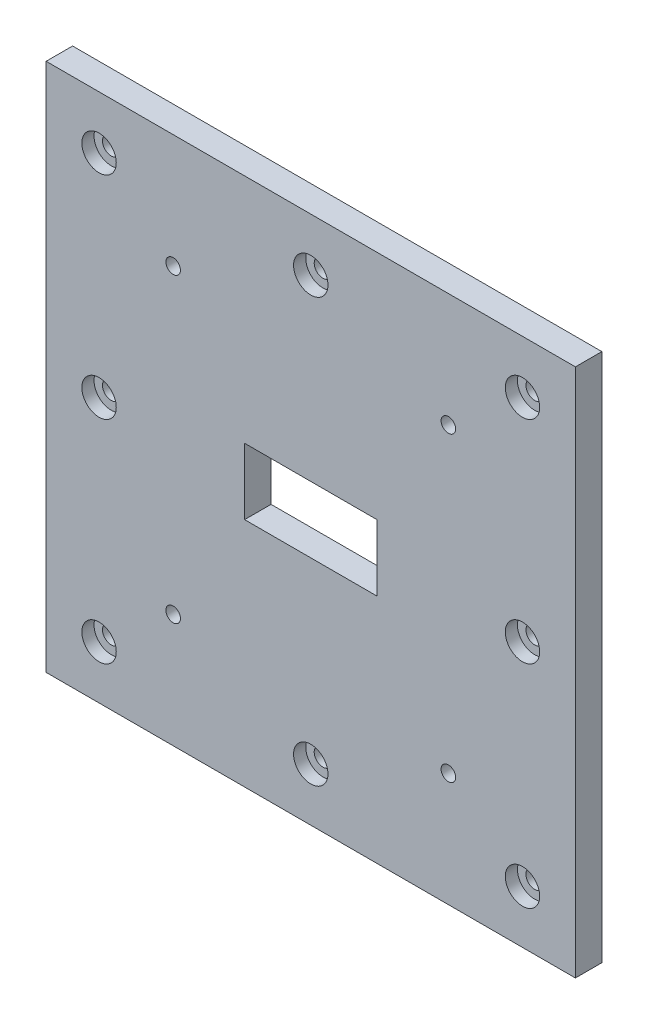
SolidWorks part; units mm, degrees
material "Aluminum"
ref_plane "Front Plane" through (0, 0, 0) normal (0, 0, 1) x (1, 0, 0)
ref_plane "Top Plane" through (0, 0, 0) normal (0, 1, 0) x (1, 0, 0)
ref_plane "Right Plane" through (0, 0, 0) normal (1, 0, 0) x (0, 0, -1)
sketch "Sketch1" plane through (0, 0, 0) normal (0, 0, 1) x (1, 0, 0)
  line L1 (100, -100) -> (-100, -100)
  line L2 (100, -100) -> (100, 100)
  line L3 (100, 100) -> (-100, 100)
  line L4 (-100, -100) -> (-100, 100)
  line L5 (100, -100) -> (-100, 100) construction
  line L6 (100, 100) -> (-100, -100) construction
  point P0 (0, 0)
  dimension "D1" = 200
  dimension "D2" = 200
extrude "Boss-Extrude1" add sketch "Sketch1" along normal blind 5 and the other way blind 5
hole_wizard "Tap Drill for M5x0.8 Tap1" positions "Sketch3" profile "Sketch2" hole size "M5x0.8" standard "ANSI Metric" end condition through all
sketch "Sketch3" plane through (0, 0, -5) normal (0, 0, -1) x (-1, 0, 0)
  line L0 (0, 0) -> (0, 100) construction
  line L1 (-100, 100) -> (100, 100) construction
  line L4 (0, 0) -> (100, 0) construction
  line L5 (100, 100) -> (100, -100) construction
  point P0 (-52, 57)
  point P3 (52, 57)
  point P6 (52, -57)
  point P9 (-52, -57)
  dimension "D1" = 52
  dimension "D2" = 52
  dimension "D3" = 52
  dimension "D4" = 57
  dimension "D5" = 57
  dimension "D6" = 57
  dimension "D7" = 57
  dimension "D8" = 52
sketch "Sketch2" plane through (52, 57, -5) normal (1, 0, 0) x (0, 1, 0)
  line L0 (0, 0) -> (0, 10)
  line L1 (0, 10) -> (2.5, 10)
  line L2 (2.5, 10) -> (2.5, 0)
  line L5 (2.5, 0) -> (0, 0)
  line L11 (0, -6.35) -> (0, 107.95) construction
  dimension "Thru Hole Dia." = 5
  dimension "Thru Hole Depth" = 10
sketch "Sketch5" plane through (0, 0, -5) normal (0, 0, -1) x (-1, 0, 0)
  line L1 (25, -12.5) -> (-25, -12.5)
  line L2 (25, -12.5) -> (25, 12.5)
  line L3 (25, 12.5) -> (-25, 12.5)
  line L4 (-25, -12.5) -> (-25, 12.5)
  line L5 (25, -12.5) -> (-25, 12.5) construction
  line L6 (25, 12.5) -> (-25, -12.5) construction
  point P0 (0, 0)
  dimension "D1" = 50
  dimension "D2" = 25
extrude "Cut-Extrude2" cut sketch "Sketch5" against normal blind 20
hole_wizard "CBORE for M6 Pan Head Screw1" positions "Sketch7" profile "Sketch6" counterbore size "M6" standard "ISO" end condition through all
sketch "Sketch7" plane through (0, 0, 5) normal (0, 0, 1) x (1, 0, 0)
  line L0 (0, 0) -> (0, 121.255) construction
  line L2 (0, 0) -> (142.7454, 0) construction
  point P0 (-80, 80)
  point P2 (-80, 0)
  point P4 (-80, -80)
  point P6 (80, 80)
  point P8 (80, 0)
  point P10 (80, -80)
  point P24 (0, 80)
  point P27 (0, -80)
  point P28 (-80, 80)
  dimension "D1" = 80
  dimension "D2" = 80
  dimension "D3" = 80
  dimension "D4" = 80
  dimension "D5" = 80
  dimension "D6" = 80
  dimension "D7" = 80
  dimension "D8" = 80
  dimension "D9" = 80
  dimension "D10" = 80
sketch "Sketch6" plane through (-80, 80, 5) normal (1, 0, 0) x (0, -1, 0)
  line L0 (0, 0) -> (0, 10)
  line L1 (0, 10) -> (3.3, 10)
  line L3 (3.3, 10) -> (3.3, 4.6)
  line L4 (3.3, 4.6) -> (6.5, 4.6)
  line L5 (6.5, 4.6) -> (6.5, 0)
  line L7 (6.5, 0) -> (0, 0)
  line L11 (0, -6.35) -> (0, 107.95) construction
  dimension "Thru Hole Dia." = 6.6
  dimension "Thru Hole Depth" = 10
  dimension "C'Bore Dia." = 13
  dimension "C'Bore Depth" = 4.6
hole_wizard "CSK for M5 Hex Socket Countersunk Cap Screw1" positions "Sketch9" profile "Sketch8" countersink size "M5" standard "ISO" end condition through all
sketch "Sketch9" plane through (0, 0, -5) normal (0, 0, -1) x (-1, 0, 0)
  point P0 (-52, 57)
  point P3 (52, 57)
  point P6 (52, -57)
  point P9 (-52, -57)
sketch "Sketch8" plane through (52, 57, -5) normal (1, 0, 0) x (0, 1, 0)
  line L0 (0, 0) -> (0, 10)
  line L1 (0, 10) -> (2.75, 10)
  line L2 (2.75, 10) -> (2.75, 2.85)
  line L3 (2.75, 2.85) -> (5.6, 0)
  line L5 (5.6, 0) -> (0, 0)
  line L6 (-2.75, 2.85) -> (-5.6, 0) construction
  line L11 (0, -6.35) -> (0, 107.95) construction
  dimension "Thru Hole Dia." = 5.5
  dimension "Thru Hole Depth" = 10
  dimension "Near C'Sink Dia." = 11.2
  dimension "Near C'Sink Angle" = 90
